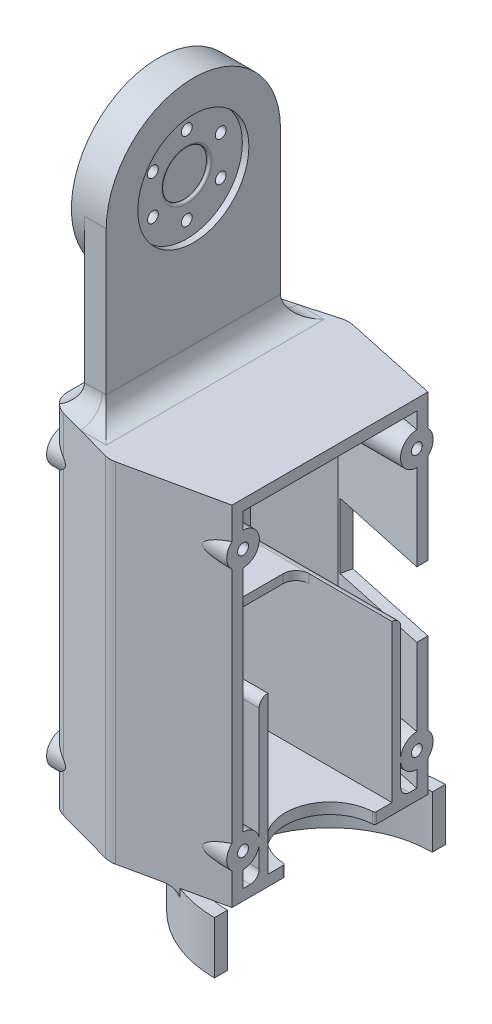
SolidWorks part; units mm, degrees
ref_plane "Front Plane" through (0, 0, 0) normal (0, 0, 1) x (1, 0, 0)
ref_plane "Top Plane" through (0, 0, 0) normal (0, 1, 0) x (1, 0, 0)
ref_plane "Right Plane" through (0, 0, 0) normal (1, 0, 0) x (0, 0, -1)
sketch "Sketch1" plane through (0, 0, 0) normal (1, 0, 0) x (0, 0, -1)
  circle A0 centre (0, 0) radius 20
  circle A1 centre (0, 0) radius 9 construction
  circle A2 centre (0, 9) radius 1.25
  circle A3 centre (7.7942, 4.5) radius 1.25
  circle A4 centre (7.7942, -4.5) radius 1.25
  circle A5 centre (0, -9) radius 1.25
  circle A6 centre (-7.7942, -4.5) radius 1.25
  circle A7 centre (-7.7942, 4.5) radius 1.25
  circle A8 centre (0, 9) radius 3
  circle A9 centre (7.7942, 4.5) radius 3
  circle A10 centre (7.7942, -4.5) radius 3
  circle A11 centre (0, -9) radius 3
  circle A12 centre (-7.7942, -4.5) radius 3
  circle A13 centre (-7.7942, 4.5) radius 3
  point P19 (0, 0)
  point P31 (0, 0)
  dimension "D1" = 40
  dimension "D2" = 18
  dimension "D3" = 2.5
  dimension "D5" = 6
  dimension "D6" = 6
  dimension "D4" = 6
extrude "Boss-Extrude1" add sketch "Sketch1" against normal blind 8 contours A0
extrude "Cut-Extrude1" cut sketch "Sketch1<3>" against normal through all contours A7 | A2 | A3 | A4 | A5 | A6 region at (0, 9, 0) region at (0, 4.5, -7.7942) region at (0, -4.5, -7.7942) region at (0, -9, 0) region at (0, -4.5, 7.7942) region at (0, 4.5, 7.7942)
sketch "Sketch1<3>" plane through (0, 0, 0) normal (1, 0, 0) x (0, 0, -1) same geometry as "Sketch1"
extrude "Cut-Extrude2" cut sketch "Sketch1<4>" against normal through all from offset 6 contours A13 A7 | A8 A2 | A9 A3 | A10 A4 | A11 A5 | A12 A6 region at (0, 9, 2.9151) region at (0, 4.5, -4.8791) region at (0, -4.5, -4.8791) region at (0, -9, 2.9151) region at (0, -4.5, 10.7094) region at (0, 4.5, 10.7094) offset against normal yes
sketch "Sketch1<4>" plane through (0, 0, 0) normal (1, 0, 0) x (0, 0, -1) same geometry as "Sketch1"
sketch "Sketch2" plane through (0, 0, 0) normal (1, 0, 0) x (0, 0, -1)
  line L2 (-20, 0) -> (-20, -38)
  line L3 (-20, -38) -> (20, -38)
  line L4 (20, 0) -> (20, -38)
  circle A0 centre (0, 0) radius 20 construction
  arc A1 (-20, 0) -> (20, 0) centre (0, 0) ccw
  dimension "D1" = 38
extrude "Boss-Extrude2" add sketch "Sketch2" against normal blind 5
sketch "Sketch3" plane through (0, -38, 0) normal (0, -1, 0) x (1, 0, 0)
  line L2 (-10, 22.5) -> (-10, -22.5)
  line L4 (31.35, 22.5) -> (31.35, -22.5)
  line L5 (0, 20) -> (0, -20) construction
  line L6 (-10, 22.5) -> (8.175, 27.5)
  line L7 (8.175, 27.5) -> (31.35, 22.5)
  line L8 (0, 0) -> (50000, 0) construction
  line L10 (8.175, -27.5) -> (31.35, -22.5)
  line L11 (-10, -22.5) -> (8.175, -27.5)
  line L13 (-8, 20) -> (-8, -20) construction
  point P17 (-10, 0)
  dimension "D1" = 31.35
  dimension "D2" = 5
  dimension "D3" = 18.175
  dimension "D4" = 45
  dimension "D5" = 2
extrude "Boss-Extrude3" add sketch "Sketch3" along normal blind 80 separate body
shell "Shell1" thickness 2.5 removed face at (31.35, -78, 0)
combine bodies "Combine1" operation type add bodies to combine 105 104
sketch "Sketch5" plane through (0, -115.5, 0) normal (0, 1, 0) x (1, 0, 0)
  line L0 (0, 0) -> (50000, 0) construction
  line L1 (31.35, 16.25) -> (-5.9, 16.25)
  line L2 (31.35, 14.25) -> (-3.9, 14.25)
  line L3 (31.35, 14.25) -> (31.35, -14.25)
  line L4 (31.35, -14.25) -> (-3.9, -14.25)
  line L5 (-3.9, 14.25) -> (-3.9, -14.25)
  line L6 (-7.5, -20.5949) -> (8.247, -24.9269)
  line L7 (8.247, -24.9269) -> (31.35, -19.9425)
  line L8 (31.35, -19.9425) -> (31.35, 19.9425)
  line L9 (31.35, 19.9425) -> (8.247, 24.9269)
  line L10 (8.247, 24.9269) -> (-7.5, 20.5949)
  line L11 (-7.5, 20.5949) -> (-7.5, -20.5949)
  line L12 (-7.5, -20.5949) -> (8.247, -24.9269)
  line L13 (8.247, -24.9269) -> (31.35, -19.9425)
  line L14 (31.35, -19.9425) -> (31.35, 19.9425)
  line L15 (31.35, 19.9425) -> (8.247, 24.9269)
  line L16 (8.247, 24.9269) -> (-7.5, 20.5949)
  line L17 (-7.5, 20.5949) -> (-7.5, -20.5949)
  line L18 (-5.9, 16.25) -> (-5.9, -16.25)
  line L19 (31.35, -16.25) -> (-5.9, -16.25)
  line M11 (31.35, -19.9425) -> (31.35, 19.9425)
  dimension "D2" = 28.5
  dimension "D3" = 35.25
  dimension "D1" = 0
  dimension "D4" = 2
extrude "Boss-Extrude4" add sketch "Sketch5" along normal blind 34 contours L18 L0 L5 L2 L1 M11 | L0 L18 L19 L14 L4 L5 region at (30.8557, -115.5, -15.25)
sketch "Sketch6" plane through (0, -81.5, 0) normal (0, 1, 0) x (1, 0, 0)
  line L0 (-5.9, 16.25) -> (31.35, 16.25)
  line L1 (31.35, 16.25) -> (31.35, -16.25)
  line L2 (31.35, -16.25) -> (-5.9, -16.25)
  line L8 (-5.9, 16.25) -> (-5.9, -16.25)
  line L9 (-5.9, -16.25) -> (31.35, -16.25)
  line L10 (31.35, -16.25) -> (31.35, -14.25)
  line L11 (31.35, -14.25) -> (-3.9, -14.25)
  line L12 (-3.9, -14.25) -> (-3.9, 14.25)
  line L13 (-3.9, 14.25) -> (31.35, 14.25)
  line L14 (31.35, 14.25) -> (31.35, 16.25)
  line L15 (31.35, 16.25) -> (-5.9, 16.25)
  line L16 (-5.9, 16.25) -> (-5.9, -16.25)
  dimension "D1" = 0
extrude "Boss-Extrude5" add sketch "Sketch6" along normal blind 2
sketch "Sketch7" plane through (0, -118, 0) normal (0, -1, 0) x (1, 0, 0)
  line L0 (31.35, -22.5) -> (31.35, 22.5) construction
  circle A0 centre (31.35, 0) radius 10.25
  dimension "D1" = 20.5
extrude "Cut-Extrude3" cut sketch "Sketch7" against normal up to next
fillet "Fillet1" radius 0.5 2 edges at (31.35, -116.75, -10.25) (31.35, -116.75, 10.25)
sketch "Sketch8" plane through (0, 0, 0) normal (1, 0, 0) x (0, 0, -1)
  circle A0 centre (0, 0) radius 12.75
  circle A1 centre (0, 0) radius 5.25
  dimension "D1" = 25.5
  dimension "D2" = 10.5
extrude "Cut-Extrude4" cut sketch "Sketch8" against normal blind 1.5 contours A0
extrude "Cut-Extrude5" cut sketch "Sketch8<3>" against normal blind 2.2 contours A1 region at (0, 0, 0)
sketch "Sketch8<3>" plane through (0, 0, 0) normal (1, 0, 0) x (0, 0, -1) same geometry as "Sketch8"
fillet "Fillet2" radius 5 4 edges at (0, -38, 0) (-2.5, -38, -20) (-2.5, -38, 20) (-5, -38, 0)
fillet "Fillet3" radius 5 4 edges at (8.175, -78, -27.5) (-10, -78, -22.5) (8.175, -78, 27.5) (-10, -78, 22.5)
fillet "Fillet4" radius 0.5 1 edges at (-1.5, 0, -5.25)
sketch "Sketch9" plane through (0, -118, 0) normal (0, -1, 0) x (1, 0, 0)
  line L0 (31.35, 14.25) -> (31.35, -14.25) construction
  line L3 (31.35, 23.5) -> (31.35, 26.5)
  line L4 (31.35, -23.5) -> (31.35, -26.5)
  arc A0 (31.35, 23.5) -> (31.35, -23.5) centre (31.35, 0) ccw
  arc A2 (31.35, 26.5) -> (31.35, -26.5) centre (31.35, 0) ccw
  dimension "D2" = 47
  dimension "D3" = 3
extrude "Boss-Extrude6" add sketch "Sketch9" along normal blind 12
fillet "Fillet6" radius 2 4 edges at (12.725, -79.5, 16.25) (12.725, -79.5, -16.25) (12.725, -115.5, -16.25) (12.725, -115.5, 16.25)
sketch "Sketch10" plane through (31.35, 0, 0) normal (1, 0, 0) x (0, 0, -1)
  line L0 (0, 0) -> (0, -50000) construction
  line L1 (-19.9425, -115.5) -> (-19.9425, -40.5) construction
  line L2 (25, -38) -> (-25, -38) construction
  line L3 (-24.6168, -118) -> (-23.245, -118) construction
  circle A0 centre (-19.9425, -48) radius 1.25
  circle A1 centre (-19.9425, -108) radius 3.75
  circle A2 centre (-19.9425, -108) radius 1.25
  circle A3 centre (-19.9425, -48) radius 3.75
  circle A4 centre (19.9425, -108) radius 3.75
  circle A5 centre (19.9425, -108) radius 1.25
  circle A6 centre (19.9425, -48) radius 3.75
  circle A7 centre (19.9425, -48) radius 1.25
  dimension "D1" = 2.5
  dimension "D2" = 10
  dimension "D3" = 7.5
  dimension "D4" = 10
extrude "Boss-Extrude7" add sketch "Sketch10" against normal through all contours A3 | A6 | A4 | A1
extrude "Cut-Extrude6" cut sketch "Sketch10<3>" against normal through all contours A0 | A7 | A5 | A2
sketch "Sketch10<3>" plane through (31.35, 0, 0) normal (1, 0, 0) x (0, 0, -1) same geometry as "Sketch10"
sketch "Sketch11" plane through (-10, 0, 0) normal (-1, 0, 0) x (0, 0, 1)
  circle A0 centre (-19.9425, -48) radius 2.5
  circle A1 centre (19.9425, -48) radius 2.5
  circle A2 centre (19.9425, -108) radius 2.5
  circle A3 centre (-19.9425, -108) radius 2.5
  dimension "D1" = 5
extrude "Cut-Extrude7" cut sketch "Sketch11" against normal blind 36.51
fillet "Fillet8" radius 2 1 edges at (4.85, -118, 0)
sketch "Sketch12" plane through (0, -79.5, 0) normal (0, 1, 0) x (1, 0, 0)
  line L1 (31.35, 14.25) -> (9.35, 14.25)
  line L2 (31.35, 14.25) -> (31.35, -14.25)
  line L3 (31.35, -14.25) -> (9.35, -14.25)
  line L4 (9.35, 14.25) -> (9.35, -14.25)
  line L5 (-5.9, -14.25) -> (31.35, -14.25) construction
  dimension "D1" = 22
extrude "Cut-Extrude8" cut sketch "Sketch12" against normal up to next
fillet "Fillet9" radius 3 2 edges at (9.35, -80.5, 14.25) (9.35, -80.5, -14.25)
sketch "Sketch13" plane through (6.0328, 0, -27.9622) normal (0.2109, 0, -0.9775) x (-0.9775, 0, -0.2109)
  line L1 (-26.4391, -71.5) -> (-3.4176, -71.5)
  line L2 (-26.4391, -71.5) -> (-26.4391, -86.5)
  line L3 (-26.4391, -86.5) -> (-3.4176, -86.5)
  line L4 (-3.4176, -71.5) -> (-3.4176, -86.5)
  line L5 (-3.4176, -118) -> (-3.4176, -38) construction
  line L6 (9.1944, -81.5) -> (-27.2178, -81.5) construction
  line L7 (-26.4391, -104.25) -> (-26.4391, -51.75) construction
  dimension "D1" = 15
  dimension "D2" = 5
extrude "Cut-Extrude9" cut sketch "Sketch13" against normal up to next
